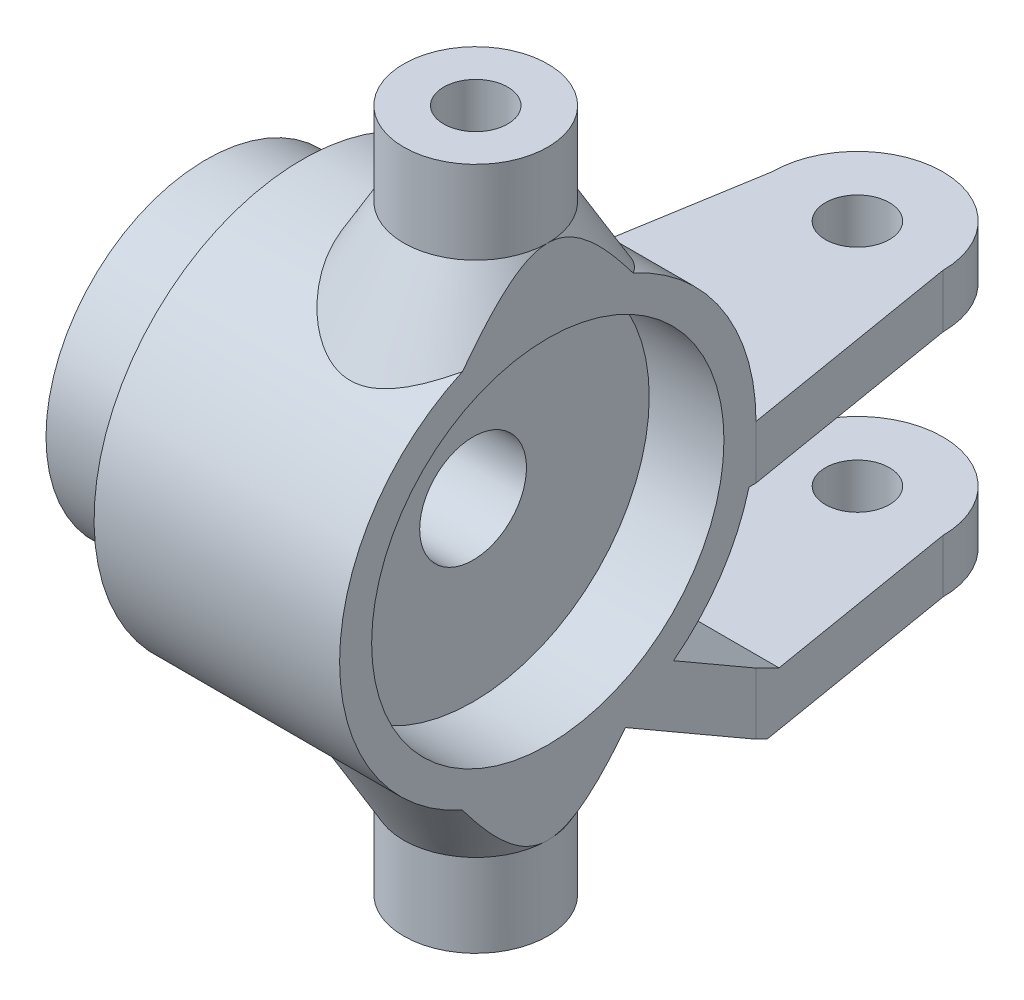
SolidWorks part; units mm, degrees
ref_plane "Front Plane" through (0, 0, 0) normal (0, 0, 1) x (1, 0, 0)
ref_plane "Top Plane" through (0, 0, 0) normal (0, 1, 0) x (1, 0, 0)
ref_plane "Right Plane" through (0, 0, 0) normal (1, 0, 0) x (0, 0, -1)
sketch "Sketch1" plane through (0, 0, 0) normal (0, 0, 1) x (1, 0, 0)
  line L0 (-29.0244, 0) -> (20.3659, 0) construction
  line L1 (-16, 2.5) -> (-16, 7.5)
  line L2 (-16, 7.5) -> (-12.5, 7.5)
  line L3 (-11.5, 8.5) -> (-11.5, 9.75)
  line L4 (-11.5, 9.75) -> (0, 9.75)
  line L5 (0, 9.75) -> (0, 8.25)
  line L6 (0, 8.25) -> (-3.5, 8.25)
  line L7 (-3.5, 8.25) -> (-3.5, 2.5)
  line L8 (-16, 2.5) -> (-3.5, 2.5)
  arc A0 (-12.5, 7.5) -> (-11.5, 8.5) centre (-12.5, 8.5) ccw
  point P5 (-16, 5)
  dimension "D8" = 1
  dimension "D1" = 5
  dimension "D2" = 15
  dimension "D3" = 19.5
  dimension "D4" = 1.5
  dimension "D5" = 4.5
  dimension "D6" = 12.5
  dimension "D7" = 16
revolve "Base Cylinder" add sketch "Sketch1" angle 360 about L0
ref_plane "Plane1" through (-3.375, 0, 0) normal (1, 0, 0) x (0, 0, -1)
sketch "Sketch2" plane through (-3.375, 0, 0) normal (1, 0, 0) x (0, 0, -1)
  line L0 (0, 16.8886) -> (0, -21.6127) construction
  line L1 (-3.375, 16) -> (-1.5, 16)
  line L2 (-1.5, 16) -> (-1.5, 9.6339)
  line L3 (-3.375, 16) -> (-3.375, 12.1113)
  line L4 (-3.375, 12.1113) -> (-5.875, 7.7812)
  circle A0 centre (0, 0) radius 9.75 construction
  arc A1 (-1.5, 9.6339) -> (-5.875, 7.7812) centre (0, 0) ccw
  point P12 (0, 9.75)
  dimension "D1" = 3
  dimension "D2" = 6.75
  dimension "D3" = 30
  dimension "D4" = 6.25
  dimension "D5" = 5
revolve "Suspension attachments" add sketch "Sketch2" angle 360 about L0
mirror "Mirror1" about plane through (0, 0, 0) normal (0, 1, 0) of "Suspension attachments"
sketch "Sketch3" plane through (0, 0, 0) normal (0, 0, 1) x (1, 0, 0)
  line L0 (0, 17.9363) -> (0, -18.3693)
  line L1 (0, -18.3693) -> (7.3027, -18.3693)
  line L2 (7.3027, -18.3693) -> (7.3027, 17.9363)
  line L3 (7.3027, 17.9363) -> (0, 17.9363)
extrude "Face Cut" cut sketch "Sketch3" against normal mid plane 20
sketch "Sketch5" plane through (0, 0, 0) normal (1, 0, 0) x (0, 0, -1)
  line L0 (9.75, 0) -> (20.25, 0)
  line L1 (20.25, 0) -> (20.25, -2.5)
  line L2 (20.25, -2.5) -> (9.424, -2.5)
  line L3 (5.887, -7.7721) -> (11.0449, -10.75)
  line L4 (11.0449, -10.75) -> (20.25, -10.75)
  line L5 (20.25, -10.75) -> (20.25, -13.25)
  line L6 (20.25, -13.25) -> (10.375, -13.25)
  line L7 (10.375, -13.25) -> (3.3099, -9.171)
  line L8 (3.375, -16) -> (3.375, -12.1113) construction
  arc A0 (4.0005, -8.8915) -> (4.0005, 8.8915) centre (0, 0) ccw construction
  arc A2 (3.3099, -9.171) -> (5.887, -7.7721) centre (0, 0) ccw
  arc A3 (9.424, -2.5) -> (9.75, 0) centre (0, 0) ccw
  point P11 (9.75, -10.75)
  point P16 (9.75, -10.75)
  point P17 (0, 0)
  point P18 (10.3247, -10.75)
  point P19 (9.75, -10.75)
  point P20 (10.3247, -10.75)
  point P21 (6.6379, -7.1415)
  point P22 (9.424, -10.75)
  point P23 (7.3218, -6.4384)
  point P24 (7.3218, -13.25)
  dimension "D1" = 10.5
  dimension "D2" = 2.5
  dimension "D3" = 2.5
  dimension "D4" = 8.25
  dimension "D5" = 2.5
  dimension "D6" = 150
  dimension "D7" = 7
extrude "Link Arms" add sketch "Sketch5" against normal up to surface (11.5 mm away) up to face at (-11.5, 0, 8.5)
sketch "Sketch6" plane through (0, 0, 0) normal (0, 1, 0) x (1, 0, 0)
  line L0 (-11.5, 20.25) -> (0, 20.25) construction
  circle A0 centre (-5.75, 20.25) radius 4
  dimension "D1" = 8
extrude "Rounded Links" add sketch "Sketch6" against normal up to surface (13.25 mm away) up to face at (-5.75, -13.25, -15.3125)
sketch "Sketch7" plane through (0, 0, 0) normal (0, 1, 0) x (1, 0, 0)
  line L0 (-9.75, 20.25) -> (-11.5, 9.75)
  line L1 (-1.75, 20.25) -> (0, 9.75)
  line L2 (0, 9.75) -> (0, 20.25)
  line L3 (0, 20.25) -> (-1.75, 20.25)
  line L4 (-11.5, 9.75) -> (-11.5, 20.25)
  line L5 (-11.5, 20.25) -> (-9.75, 20.25)
  circle A0 centre (-5.75, 20.25) radius 1.5
  arc A1 (-1.75, 20.25) -> (-9.75, 20.25) centre (-5.75, 20.25) ccw construction
  point P14 (-5.8285, 20.25)
  dimension "D1" = 3
extrude "Trim 1" cut sketch "Sketch7" against normal up to surface (13.25 mm away) up to face at (-5.75, -13.25, -17.625)
sketch "Sketch8" plane through (1.5811, 0, -0.2635) normal (0.9864, 0, -0.1644) x (-0.1644, 0, -0.9864)
  line L0 (16.9198, -2.5) -> (16.9198, -10.75)
  line L1 (16.9198, -2.5) -> (16.9198, -10.75) construction
  line L2 (20.2622, -10.75) -> (10.9301, -10.75) construction
  line L3 (16.9198, -10.75) -> (24.9198, -10.75)
  line L4 (24.9198, -13.25) -> (24.9198, 0) construction
  line L5 (24.9198, -10.75) -> (24.9198, -2.5)
  line L6 (24.9198, -2.5) -> (16.9198, -2.5)
extrude "Trim 2" cut sketch "Sketch8" against normal mid plane 30
